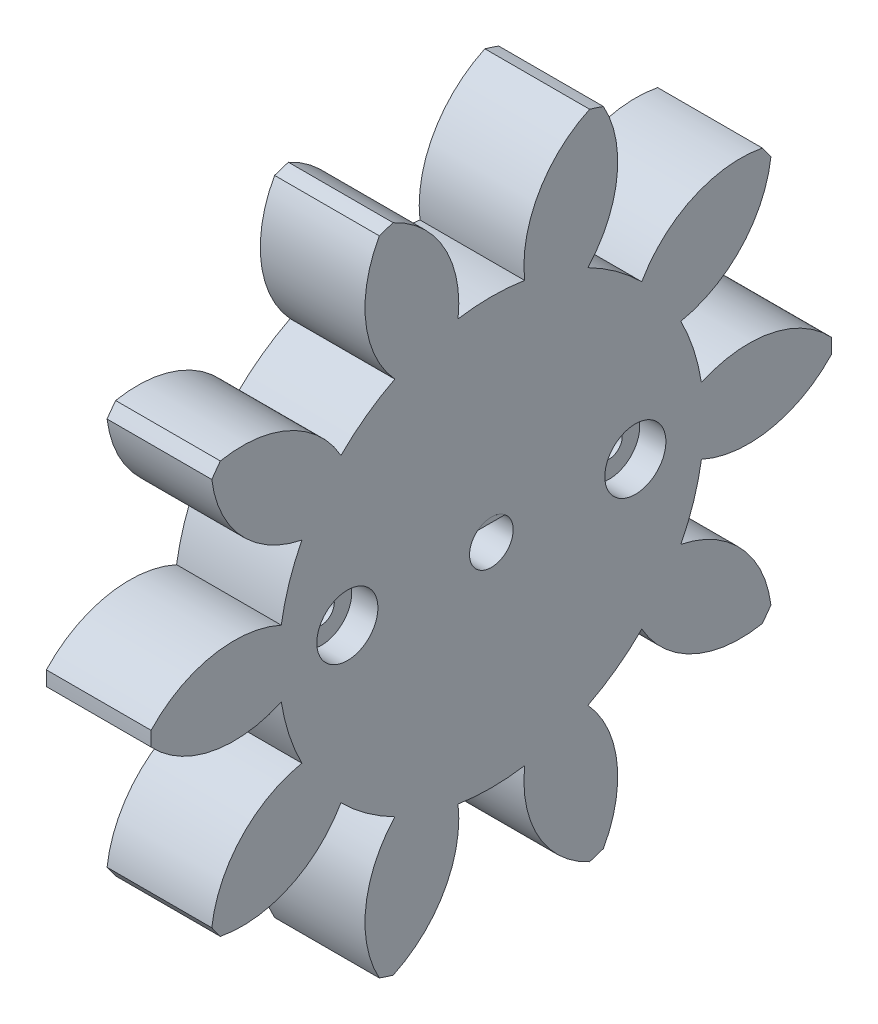
SolidWorks part; units mm, degrees
ref_plane "Plane1" through (0, 0, 0) normal (0, 0, 1) x (1, 0, 0)
ref_plane "Plane2" through (0, 0, 0) normal (0, 1, 0) x (1, 0, 0)
ref_plane "Plane3" through (0, 0, 0) normal (1, 0, 0) x (0, 0, -1)
other "Configuration Table"
sketch "HoldingSke" plane through (0, 0, 0) normal (0, 1, 0) x (1, 0, 0)
  line L0 (0, 0) -> (0.1515, -0.0267)
  line L1 (-15, 0) -> (100, 0) construction
  line L2 (0, 0) -> (-2.1039, 2.3779)
  line L3 (0, 0) -> (-11.863, 4.5341)
  line L4 (0, 0) -> (8.5048, 1.4996)
  line L5 (0, 0) -> (-46.8476, -17.4728)
  line L6 (0, 0) -> (-9.9476, -6.7116)
  line L7 (-2.1039, 2.3779) -> (8.6586, 51.2059)
  line L8 (-76.2, 54.61) -> (-75.7, 54.61)
  line L9 (-71.009, 38.7566) -> (-53.1078, 45.2721)
  line L10 (-76.2, 71.12) -> (104.1128, 71.12)
  line L11 (0, 0) -> (-12, 0)
  line L12 (-76.2, 101.6) -> (-75.981, 101.6)
  line L13 (24.9733, 27.94) -> (52.9518, 28.4284)
  line L14 (24.9733, 27.94) -> (24.9743, 27.94)
  line L15 (24.9733, 27.94) -> (100.4006, 29.5858)
  line L16 (-63.627, -6.5) -> (-12.827, -6.5)
  circle A0 centre (0, 0) radius 1.5
  circle A1 centre (0, 0) radius 24.374
  circle A2 centre (0, 0) radius 37.5
  circle A3 centre (0, 0) radius 1.5
  dimension "Num_teeth" = 10
  dimension "Pitch_radius" = 180.3128
  dimension "Width" = 12
  dimension "Thickness" = 12
sketch "BasProSke" plane through (0, 0, 0) normal (0, 1, 0) x (1, 0, 0)
  line L0 (-10, 0) -> (60, 0) construction
  line L1 (0, 0) -> (0, 39)
  line L2 (0, 0) -> (12, 0)
  line L3 (12, 0) -> (12, 39)
  line L4 (12, 39) -> (0, 39)
  dimension "Thickness" = 12
  dimension "Diameter" = 78
revolve "Base-Revolve" add sketch "BasProSke" angle 360 about L0
sketch "TooCutSke" plane through (0, 0, 0) normal (1, 0, 0) x (0, 0, -1)
  line L1 (0, 0) -> (0, 107) construction
  line L2 (0, 0) -> (-5.4666, 32.0369) construction
  line L3 (0, 0) -> (-19.8749, 61.1686) construction
  line L4 (-5.4666, 32.0369) -> (-9.9374, 30.5843) construction
  arc A0 (3.8158, 24.0735) -> (-3.8158, 24.0735) centre (0, 0) ccw
  arc A1 (11.2922, 37.356) -> (-11.2922, 37.356) centre (0, 0) ccw
  circle A2 centre (0, 0) radius 32.5 construction
  circle A3 centre (0, 0) radius 30.54 construction
  arc A4 (-3.8158, 24.0735) -> (-11.2922, 37.356) centre (-16.7318, 25.5488) ccw
  arc A5 (11.2922, 37.356) -> (3.8158, 24.0735) centre (16.7318, 25.5488) ccw
extrude "ToothCut" cut sketch "TooCutSke" along normal through all
fillet "Breaks" [suppressed] radius 0.13 tangent propagation no
fillet "RootFillets" [suppressed] radius 1.626
pattern_circular "TeethCuts" count 10 every 36 about axis through (-10, 0, 0) along (1, 0, 0) of "ToothCut", "RootFillets", "Breaks"
sketch "HubNeaOneSke" plane through (0, 0, 0) normal (-1, 0, 0) x (0, 0, 1)
  circle A0 centre (0, 0) radius 24.374
  dimension "Diameter" = 48.748
extrude "HubNearOne" [suppressed] add sketch "HubNeaOneSke" along normal blind 38.0001
sketch "HubNeaBotSke" plane through (0, 0, 0) normal (-1, 0, 0) x (0, 0, 1)
  circle A0 centre (0, 0) radius 24.374
  dimension "Diameter" = 48.748
extrude "HubNearBoth" [suppressed] add sketch "HubNeaBotSke" along normal blind 19
ref_plane "FarPln" through (12, 0, 0) normal (1, 0, 0) x (0, 0, -1)
sketch "HubFarSke" plane through (12, 0, 0) normal (1, 0, 0) x (0, 0, -1)
  circle A0 centre (0, 0) radius 24.374
  dimension "Diameter" = 48.748
extrude "HubFar" [suppressed] add sketch "HubFarSke" along normal blind 19
sketch "BorSke" plane through (0, 0, 0) normal (1, 0, 0) x (0, 0, -1)
  circle A0 centre (0, 0) radius 1.5
  dimension "Diameter" = 3
extrude "Bore" cut sketch "BorSke" along normal mid plane 100.0001
sketch "KeySke" plane through (0, 0, 0) normal (1, 0, 0) x (0, 0, -1)
  line L0 (-0.6, 0) -> (-0.6, 2)
  line L1 (-0.6, 2) -> (0.6, 2)
  line L2 (0.6, 2) -> (0.6, 0)
  line L3 (0, 0) -> (0, 34) construction
  line L4 (-0.6, 0) -> (0.6, 0)
  dimension "Width" = 1.2
extrude "Keyway" [suppressed] cut sketch "KeySke" along normal mid plane 100.0001
pattern_circular "Keyway2" [suppressed] count 2 every 90 about axis through (-10, 0, 0) along (1, 0, 0)
sketch "Croquis1" plane through (12, 0, 0) normal (1, 0, 0) x (0, 1, 0)
  circle A0 centre (0, 0) radius 2.5
  dimension "D1" = 5
extrude "Cortar-Extruir1" cut sketch "Croquis1" against normal through all
sketch "Croquis2" plane through (12, 0, 0) normal (1, 0, 0) x (0, 0, -1)
  line L0 (-1.5644, 1.95) -> (1.5644, 1.95)
  circle A0 centre (0, 0) radius 2.5
  point P5 (0, -2.5)
  circle M3 centre (0, 0) radius 2.5
  dimension "D1" = 4.45
extrude "Saliente-Extruir1" add sketch "Croquis2" against normal blind 12 separate body contours L0 M3 region at (12, 2.1722, 0)
sketch "Croquis3" plane through (12, 0, 0) normal (1, 0, 0) x (0, 0, -1)
  circle A0 centre (-16.5, 0) radius 1.5
  circle A1 centre (-16.5, 0) radius 3.5
  point P2 (0, 0)
  dimension "D1" = 3
  dimension "D2" = 16.5
  dimension "D3" = 7
extrude "Cortar-Extruir2" cut sketch "Croquis3" against normal blind 12 contours A0 region at (12, 0, 16.5)
extrude "Cortar-Extruir3" cut sketch "Croquis3<3>" against normal blind 3 contours A1 A0 region at (12, 0, 19.901)
sketch "Croquis3<3>" plane through (12, 0, 0) normal (1, 0, 0) x (0, 0, -1) same geometry as "Croquis3"
mirror "Simetría1" about plane through (0, 0, 0) normal (0, 0, 1) of "Cortar-Extruir2", "Cortar-Extruir3"
equation "' \"Module@HoldingSke\" = 6.35"
equation "' \"Num_teeth@HoldingSke\" = 12"
equation "' \"Ap@HoldingSke\" =  20"
equation "' \"Ap@HoldingSke\" = 20"
equation "' \"Width@HoldingSke\" = 0.5 * 25.4"
equation "' \"Hub_dia@HoldingSke\"= 1 * 25.4"
equation "' \"Hub_dia@HoldingSke\" = 1 * 25.4"
equation "' \"Overall_len@HoldingSke\" = 1.0 * 25.4"
equation "' \"Bore@HoldingSke\" = 0.75 * 25.4"
equation "' \"T_dim@HoldingSke\" = 0.1 * 25.4"
equation "' \"Width@KeySke\" = 0.25 * 25.4"
equation "' \"Show_teeth@HoldingSke\" = 13"
equation "' \"Backlash@HoldingSke\" = 0.009 * 25.4"
equation "' \"Addendum_fac@HoldingSke\" = 1.0"
equation "' \"Dedendum_fac@HoldingSke\" = 1.25"
equation "' \"Dedendum_add@HoldingSke\" = 0.00005 * 25.4"
equation "' \"Clearance_fac@HoldingSke\" = 0.25"
equation "\"Pitch@HoldingSke\" = 1 / \"Module@HoldingSke\""
equation "\"Overcut_dia@TooCutSke\" = (\"Num_teeth@HoldingSke\" + 2 * \"Addendum_fac@HoldingSke\") / \"Pitch@HoldingSke\" + 0.002 * 25.4"
equation "\"Pitch_dia@TooCutSke\" = \"Num_teeth@HoldingSke\" / \"Pitch@HoldingSke\""
equation "\"Base_dia@TooCutSke\" = \"Num_teeth@HoldingSke\" / \"Pitch@HoldingSke\" * cos((\"Ap@HoldingSke\"  * 3.14159265 / 180))"
equation "\"Root_dia@TooCutSke\" = (\"Num_teeth@HoldingSke\" + 2) / \"Pitch@HoldingSke\" - 2 * (\"Addendum_fac@HoldingSke\" + \"Dedendum_fac@HoldingSke\") / \"Pitch@HoldingSke\" - \"Dedendum_add@HoldingSke\" * 2"
equation "\"Half_ang@TooCutSke\" = 180 / \"Num_teeth@HoldingSke\""
equation "\"Half_CT@TooCutSke\" = \"Num_teeth@HoldingSke\" / \"Pitch@HoldingSke\" * sin((3.14159265 / 2 / \"Num_teeth@HoldingSke\")) / 2 - 7 * \"Backlash@HoldingSke\" / 4"
equation "\"Flank_rad@TooCutSke\" = \"Num_teeth@HoldingSke\" / \"Pitch@HoldingSke\" / 5"
equation "\"Radius@RootFillets\" = \"Clearance_fac@HoldingSke\" / \"Pitch@HoldingSke\" + \"Dedendum_add@HoldingSke\""
equation "\"Break_rad@Breaks\" = 0.02 / \"Pitch@HoldingSke\""
equation "\"Thickness@HoldingSke\" = \"Width@HoldingSke\""
equation "\"OAL@HoldingSke\" = \"Thickness@HoldingSke\""
equation "\"MHD@HoldingSke\" = (\"Num_teeth@HoldingSke\" + 2) / \"Pitch@HoldingSke\" - 2 * (\"Addendum_fac@HoldingSke\" + \"Dedendum_fac@HoldingSke\")  / \"Pitch@HoldingSke\" - \"Dedendum_add@HoldingSke\" * 2"
equation "\"MBD@HoldingSke\" = (\"Num_teeth@HoldingSke\" + 2) / \"Pitch@HoldingSke\" - 2 * (\"Addendum_fac@HoldingSke\" + \"Dedendum_fac@HoldingSke\")  / \"Pitch@HoldingSke\" - \"Dedendum_add@HoldingSke\" * 2 - 0.002 * 25.4"
equation "\"MHD@HoldingSke\" = ((sgn( \"MHD@HoldingSke\" - \"Hub_dia@HoldingSke\" )-1)*( \"MHD@HoldingSke\" - \"Hub_dia@HoldingSke\" ))/-2+ \"Hub_dia@HoldingSke\""
equation "\"MBD@HoldingSke\" = ((sgn( \"MBD@HoldingSke\" - \"Bore@HoldingSke\" )-1)*( \"MBD@HoldingSke\" - \"Bore@HoldingSke\" ))/-2+ \"Bore@HoldingSke\""
equation "\"OAL@HoldingSke\" = ((sgn( \"OAL@HoldingSke\" - \"Overall_len@HoldingSke\" )+1)*( \"OAL@HoldingSke\" - \"Overall_len@HoldingSke\" ))/2 + \"Overall_len@HoldingSke\" + 0.000002 * 25.4"
equation "\"Num_teeth@TeethCuts\" = int( \"Show_teeth@HoldingSke\" ) + 1"
equation "\"Num_teeth@TeethCuts\" = ((sgn( \"Num_teeth@TeethCuts\" - \"Num_teeth@HoldingSke\" )-1)*( \"Num_teeth@TeethCuts\" - \"Num_teeth@HoldingSke\" ))/-2+ \"Num_teeth@HoldingSke\""
equation "\"Num_teeth@TeethCuts\" = ((sgn( \"Num_teeth@TeethCuts\" - 2.0)+1)*( \"Num_teeth@TeethCuts\" - 2.0))/2 +2.0"
equation "\"Angle@TeethCuts\" = 360.0 / \"Num_teeth@HoldingSke\""
equation "\"Diameter@BasProSke\" = (\"Num_teeth@HoldingSke\" + 2 * \"Addendum_fac@HoldingSke\") / \"Pitch@HoldingSke\""
equation "\"Thickness@BasProSke\"  = \"Thickness@HoldingSke\""
equation "' \"Fillet_rad@BasProSke\" =  \"Thickness@HoldingSke\" * 0.05"
equation "' \"Fillet_rad@BasProSke\" = \"Thickness@HoldingSke\" * 0.05"
equation "\"MHD@HoldingSke\" = ((sgn( \"MHD@HoldingSke\" - \"Root_dia@TooCutSke\" )-1)*( \"MHD@HoldingSke\" - \"Root_dia@TooCutSke\" ))/-2+ \"Root_dia@TooCutSke\""
equation "\"Diameter@HubNeaOneSke\" = \"MHD@HoldingSke\""
equation "\"Length@HubNearOne\" = \"OAL@HoldingSke\" - \"Thickness@BasProSke\""
equation "\"Diameter@HubNeaBotSke\" = \"MHD@HoldingSke\""
equation "\"Length@HubNearBoth\" = ( \"OAL@HoldingSke\" - \"Thickness@BasProSke\" ) / 2.0"
equation "\"Thickness@FarPln\" = \"Thickness@BasProSke\""
equation "\"Diameter@HubFarSke\" = \"MHD@HoldingSke\""
equation "\"Length@HubFar\" = ( \"OAL@HoldingSke\" - \"Thickness@BasProSke\" ) / 2.0"
equation "\"Diameter@BorSke\" = \"MBD@HoldingSke\""
equation "\"D1@Bore\" = \"OAL@HoldingSke\" * 2.0"
equation "\"D1@Keyway\" = \"OAL@HoldingSke\" * 2.0"
equation "\"Offset@KeySke\" = \"T_dim@HoldingSke\" + \"MBD@HoldingSke\" / 2.0"
